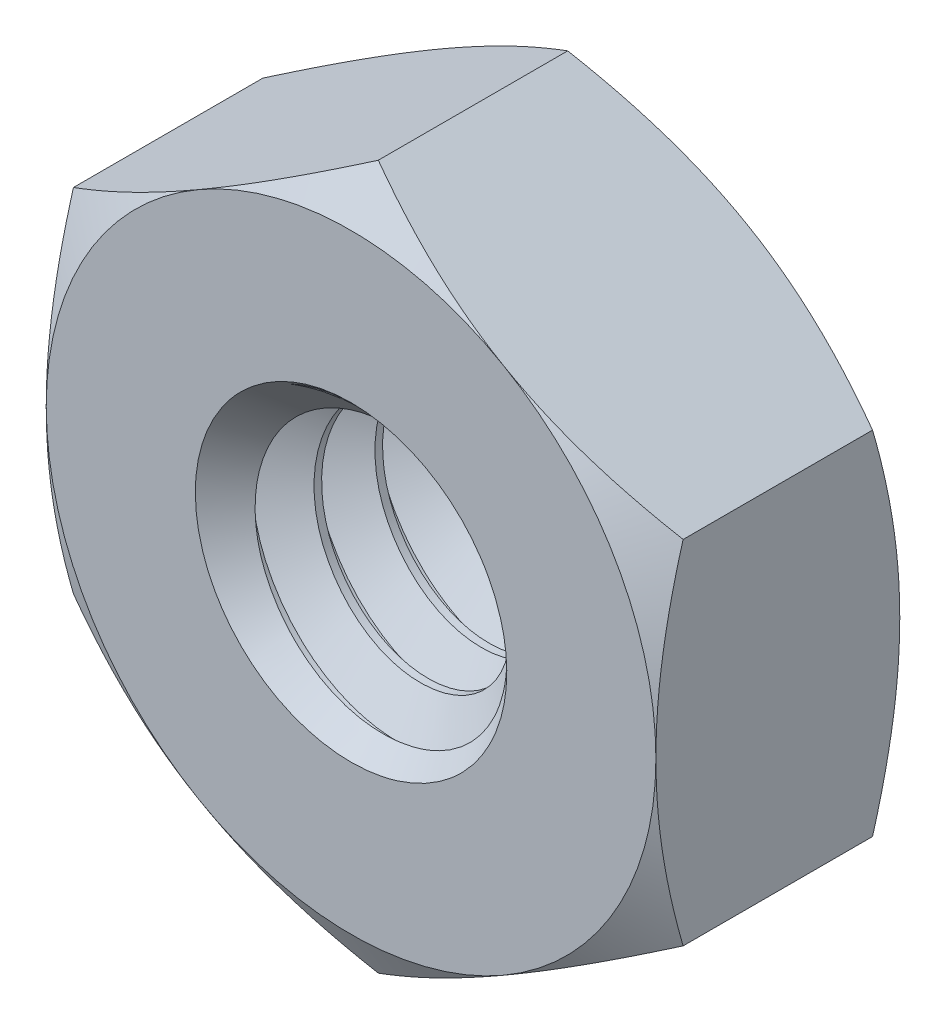
SolidWorks part; units mm, degrees
ref_plane "Front Plane" through (0, 0, 0) normal (0, 0, 1) x (1, 0, 0)
ref_plane "Top Plane" through (0, 0, 0) normal (0, 1, 0) x (1, 0, 0)
ref_plane "Right Plane" through (0, 0, 0) normal (1, 0, 0) x (0, 0, -1)
sketch "Sketch1" plane through (0, 0, 0) normal (1, 0, 0) x (0, 0, -1)
  line L0 (-0.8, 0) -> (0.8, 0) construction
  line L1 (-0.8, -2) -> (-0.8, 2) construction
  line L2 (0.8, -2) -> (0.8, 2) construction
  line L3 (-0.8, -1) -> (-0.8, 1) construction
  line L4 (-1.175, 1.0433) -> (-0.975, 0.6969) construction
  line L5 (-0.975, 0.6969) -> (-0.775, 1.0433) construction
  line L6 (-0.775, 1.0433) -> (-1.175, 1.0433) construction
  line L7 (-1.1625, 1.0217) -> (-0.7875, 1.0217) construction
  line L8 (-1.15, 1) -> (-0.8, 1) construction
  line L9 (-1, 0.7402) -> (-0.95, 0.7402) construction
  line L10 (-0.975, 0.7402) -> (-0.975, 0.6969) construction
  line L11 (-0.975, 1.0433) -> (-0.975, 1) construction
  point P4 (0, 0)
  point P7 (-0.8, 0)
  point P11 (0.8, 0)
  point P14 (-0.8, 0)
  point P26 (-0.975, 1.0217)
  point P27 (-0.8, -1)
  dimension "Height" = 1.6
  dimension "Width" = 4
  dimension "Thread OD" = 2
  dimension "D1" = 60
  dimension "Pitch" = 0.4
  dimension "D2" = 0.05
sketch "Sketch2" plane through (0, 0, 0) normal (0, 0, 1) x (1, 0, 0)
  line L1 (0, 2.3094) -> (-2, 1.1547)
  line L2 (-2, 1.1547) -> (-2, -1.1547)
  line L3 (-2, -1.1547) -> (0, -2.3094)
  line L4 (0, -2.3094) -> (2, -1.1547)
  line L5 (2, -1.1547) -> (2, 1.1547)
  line L6 (2, 1.1547) -> (0, 2.3094)
  circle A0 centre (0, 0) radius 2 construction
  circle A1 centre (0, 0) radius 1
extrude "Boss-Extrude1" add sketch "Sketch2" along normal up to vertex (0.8 mm away) and the other way up to vertex (0.8 mm away) up to point (0, -2, 0.8) other way up to point (0, -2, -0.8)
sketch "Sketch3" plane through (0, 0, 0.8) normal (0, 0, 1) x (1, 0, 0)
  circle A0 centre (0, 0) radius 2
extrude "Cut-Extrude1" cut sketch "Sketch3" against normal through all draft 60 flip side to cut
mirror "Mirror1" about plane through (0, 0, 0) normal (0, 0, 1) of "Cut-Extrude1"
ref_axis "Center Axis 1" through (0, 0, -10.9016) along (0, 0, 1)
ref_plane "Contact Plane 1" through (0, 0, 0.8) normal (0, 0, 1) x (1, 0, 0)
ref_plane "Contact Plane 2" through (0, 0, -0.8) normal (0, 0, -1) x (-1, 0, 0)
sketch "Sketch4" plane through (0, 0, 0) normal (1, 0, 0) x (0, 0, -1)
  line L1 (-1.1625, 1.0217) -> (-1, 0.7402)
  line L2 (-1, 0.7402) -> (-0.95, 0.7402)
  line L3 (-0.95, 0.7402) -> (-0.7875, 1.0217)
  line L4 (-1.1625, 1.0217) -> (-0.7875, 1.0217) construction
  line L5 (-1.1625, 1.0217) -> (-0.7875, 1.0217)
sketch "Sketch5" plane through (0, 0, 0.8) normal (0, 0, 1) x (1, 0, 0)
  circle A0 centre (0, 0) radius 1 construction
  circle A1 centre (0, 0) radius 1
curve "Helix/Spiral1" pitch 0.4 height 2 radius 1 centre (0, 0, 0.8) axis (0, 0, -1) start towards (0, 1, 0)
sweep "Sweep1" add profiles "Sketch4" path "Helix/Spiral1"
sketch "Sketch6" plane through (0, 0, 0.8) normal (0, 0, 1) x (1, 0, 0)
  circle A1 centre (0, 0) radius 1.0217
extrude "Cut-Extrude2" cut sketch "Sketch6" along normal through all and the other way through all draft 45
sketch "Sketch7" plane through (0, 0, -0.8) normal (0, 0, -1) x (-1, 0, 0)
  circle A1 centre (0, 0) radius 1.0217
  circle A2 centre (0, 0) radius 1.0217
  dimension "D1" = 0
extrude "Cut-Extrude3" cut sketch "Sketch7" along normal through all and the other way through all draft 45
ref_axis "Z" through (0, 0, -1.0304) along (0, 0, 1)
equation "\"D2@Sketch1\"=\"Pitch@Sketch1\"/8"
equation "\"D4@Helix/Spiral1\"=\"Pitch@Sketch1\""
equation "\"D3@Helix/Spiral1\"=\"Height@Sketch1\"+\"Pitch@Sketch1\""
